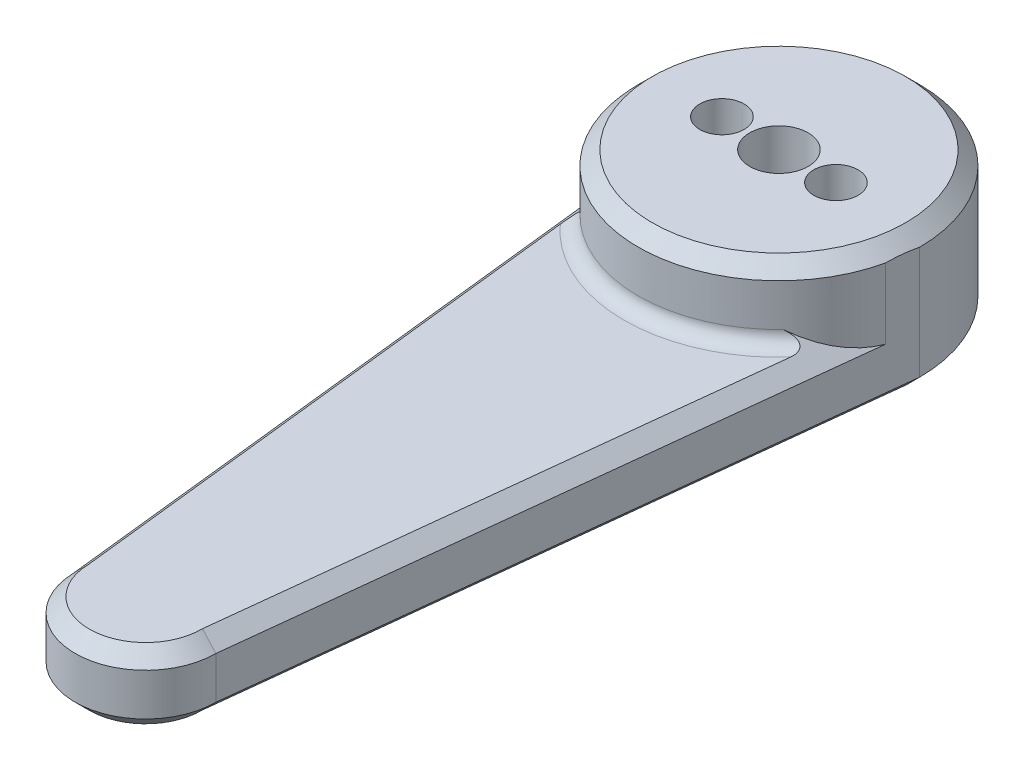
SolidWorks part; units mm, degrees
ref_plane "Front Plane" through (0, 0, 0) normal (0, 0, 1) x (1, 0, 0)
ref_plane "Top Plane" through (0, 0, 0) normal (0, 1, 0) x (1, 0, 0)
ref_plane "Right Plane" through (0, 0, 0) normal (1, 0, 0) x (0, 0, -1)
sketch "Sketch1" plane through (0, 0, 0) normal (0, 1, 0) x (1, 0, 0)
  line L0 (0, 0) -> (0, -90) construction
  line L1 (0, 0) -> (0, -90) construction
  line L4 (-9.9945, -90.3318) -> (-20, 0)
  line L5 (10, -90) -> (20, 0)
  arc A0 (-19.5152, -4.3769) -> (19.5122, -4.3902) centre (0, 0) ccw construction
  arc A2 (-9.9945, -90.3318) -> (10, -90) centre (0, -90) ccw
  arc A3 (20, 0) -> (-20, 0) centre (0, 0) ccw
  point P5 (0, -45)
  dimension "D1" = 40
  dimension "D3" = 10
  dimension "D2" = 90
extrude "Boss-Extrude1" add sketch "Sketch1" along normal blind 20
sketch "Sketch2" plane through (0, 20, 0) normal (0, 1, 0) x (1, 0, 0)
  circle A0 centre (0, 0) radius 4.15
  dimension "D1" = 8.3
extrude "Cut-Extrude1" cut sketch "Sketch2" against normal blind 20
sketch "Sketch4" plane through (0, 20, 0) normal (0, 1, 0) x (1, 0, 0)
  line L0 (-13.0965, -103.1668) -> (-42.6436, -72.342)
  line L1 (-13.0965, -103.1668) -> (13.2562, -103.1668)
  line L2 (13.2562, -103.1668) -> (28.2693, -10.6925)
  line L3 (28.2693, -10.6925) -> (20, 0)
  line L4 (-42.6436, -72.342) -> (-42.6436, -20.5948)
  line L5 (-42.6436, -20.5948) -> (-42.6436, 0)
  line L6 (-42.6436, 0) -> (-20, 0)
  arc A0 (-20, 0) -> (20, 0) centre (0, 0) ccw
extrude "Cut-Extrude3" cut sketch "Sketch4" against normal blind 10
chamfer "Chamfer1" distance 2 angle 45 7 edges at (0.1659, 10, 99.9986) (14.7561, 10, 47.1951) (15, 0, 45) (0.1659, 0, 99.9986) (-14.9972, 0, 45.1659) (0, 20, -20) (0, 0, -20)
fillet "Fillet1" radius 2 1 edges at (-0.0043, 10, 20)
sketch "Sketch5" plane through (0, 20, 0) normal (0, 1, 0) x (1, 0, 0)
  circle A0 centre (8.1, 0) radius 3.15
  circle A1 centre (-8.1, 0) radius 3.15
  dimension "D2" = 6.3
  dimension "D4" = 6.3
  dimension "D1" = 8.1
  dimension "D3" = 8.1
extrude "Cut-Extrude4" cut sketch "Sketch5" against normal blind 18
